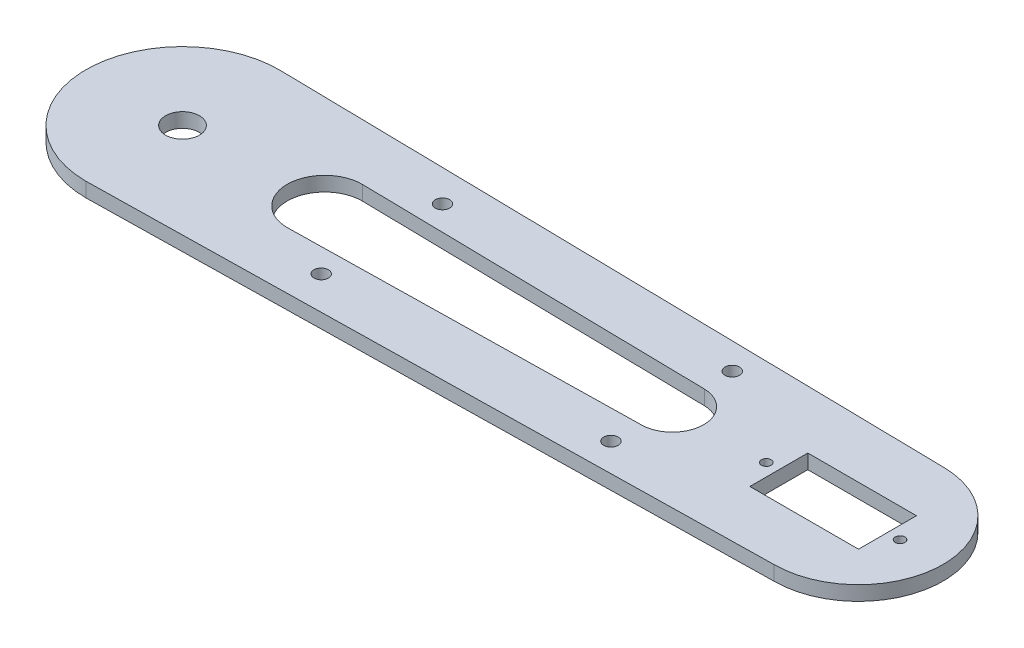
SolidWorks part; units mm, degrees
ref_plane "Front Plane" through (0, 0, 0) normal (0, 0, 1) x (1, 0, 0)
ref_plane "Top Plane" through (0, 0, 0) normal (0, 1, 0) x (1, 0, 0)
ref_plane "Right Plane" through (0, 0, 0) normal (1, 0, 0) x (0, 0, -1)
sketch "Sketch1" plane through (0, 0, 0) normal (0, 1, 0) x (1, 0, 0)
  line L0 (0.3571, 19.9968) -> (140.3125, 17.4972)
  line L1 (140, -17.5) -> (0, -20)
  circle A0 centre (0, 0) radius 20
  circle A1 centre (140, 0) radius 17.5
  point P11 (70.9941, 1.1797)
  dimension "D1" = 140
  dimension "D2" = 40
  dimension "D3" = 35
extrude "Boss-Extrude1" add sketch "Sketch1" along normal blind 3 contours L1 A0 | A1 L0 A0 L1 | A1 A0 region at (70.0919, 0, -0.0019) region at (0, 0, 0) region at (140, 0, 0)
sketch "Sketch2" plane through (0, 3, 0) normal (0, 1, 0) x (1, 0, 0)
  line L1 (123.5, 6) -> (146, 6)
  line L2 (123.5, 6) -> (123.5, -6)
  line L3 (123.5, -6) -> (146, -6)
  line L4 (146, 6) -> (146, -6)
  circle A0 centre (0, 0) radius 3.5
  circle A1 centre (140, 0) radius 3.5
  circle A2 centre (148.6, 0) radius 1
  circle A3 centre (120.9, 0) radius 1
  point P15 (146, 0)
  dimension "D1" = 7
  dimension "D2" = 7
  dimension "D3" = 2
  dimension "D6" = 27.7
  dimension "D7" = 2.6
  dimension "D8" = 8.6
  dimension "D4" = 12
  dimension "D5" = 22.5
extrude "Cut-Extrude1" cut sketch "Sketch2" against normal through all
sketch "Sketch4" plane through (0, 3, 0) normal (0, 1, 0) x (1, 0, 0)
  line L0 (101.2839, 6.7707) -> (29.173, 8.0586)
  line L1 (29.1576, -7.4774) -> (101.4946, -6.1857)
  arc A6 (29.173, 8.0586) -> (29.1576, -7.4774) centre (29.1653, 0.2906) ccw
  arc A7 (101.2839, 6.7707) -> (101.0524, -6.1936) centre (101.1578, 0.2888) cw
  dimension "D2" = 7.768
  dimension "D3" = 6.4832
  dimension "D1" = 72.337
  dimension "D4" = 2.046
extrude "Cut-Extrude3" cut sketch "Sketch4" against normal through all contours A7 L0 A6 L1 | A7 L0 A6 L1 region at (63.243, 3, -0.2906)
sketch "Sketch8" plane through (0, 3, 0) normal (0, 1, 0) x (1, 0, 0)
  circle A0 centre (0, 0) radius 1.5
  circle A1 centre (140, 0) radius 3.5
  dimension "D1" = 3
  dimension "D2" = 7
extrude "Cut-Extrude6" cut sketch "Sketch8" against normal through all rebuild error yes
sketch "Sketch9" plane through (0, 3, 0) normal (0, 1, 0) x (1, 0, 0)
  circle A0 centre (140, 0) radius 4.4965
extrude "Cut-Extrude7" cut sketch "Sketch9" against normal blind 10
sketch "Sketch10" plane through (0, 3, 0) normal (0, 1, 0) x (1, 0, 0)
  line L0 (70.9941, 1.1797) -> (70.9941, 35.0995) construction
  line L1 (101.2839, 6.7707) -> (29.173, 8.0586) construction
  line L2 (29.1576, -7.4774) -> (101.4946, -6.1857) construction
  circle A0 centre (40.9941, 12.8483) radius 1.5
  circle A1 centre (40.9941, -12.2668) radius 1.5
  circle A2 centre (100.9941, -12.2668) radius 1.5
  circle A3 centre (100.9941, 12.8483) radius 1.5
  dimension "D2" = 3
  dimension "D3" = 5
  dimension "D4" = 30
  dimension "D1" = 5
extrude "Cut-Extrude8" cut sketch "Sketch10" against normal blind 10
